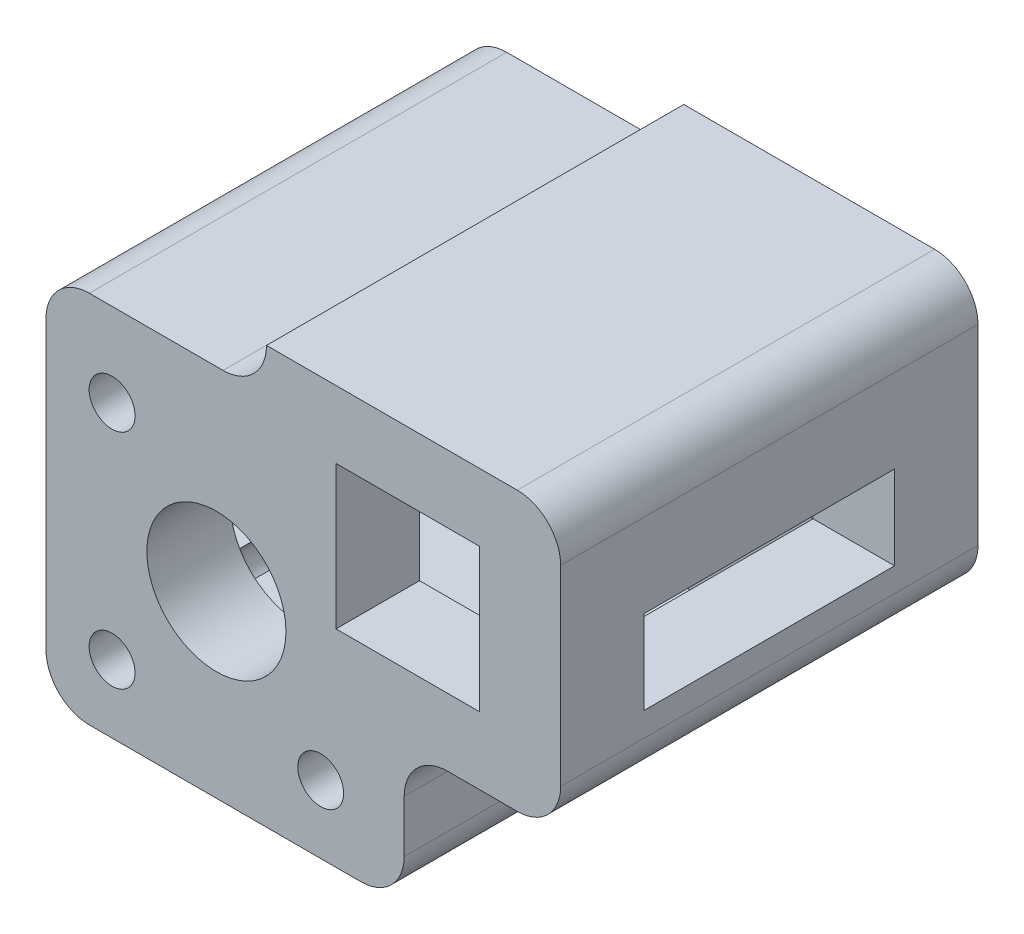
SolidWorks part; units mm, degrees
material "ABS"
ref_plane "前视基准面" through (0, 0, 0) normal (0, 0, 1) x (1, 0, 0)
ref_plane "上视基准面" through (0, 0, 0) normal (0, 1, 0) x (1, 0, 0)
ref_plane "右视基准面" through (0, 0, 0) normal (1, 0, 0) x (0, 0, -1)
sketch "草图1" plane through (0, 0, 0) normal (0, 0, 1) x (1, 0, 0)
  line L1 (-18.5, 15) -> (18.5, 15)
  line L2 (-18.5, 15) -> (-18.5, -15)
  line L3 (-18.5, -15) -> (18.5, -15)
  line L4 (18.5, 15) -> (18.5, -15)
  line L5 (-18.5, 15) -> (18.5, -15) construction
  line L6 (-18.5, -15) -> (18.5, 15) construction
  line L11 (2.5, 10) -> (12.5, 10) construction
  line L12 (2.5, 10) -> (2.5, 0) construction
  line L17 (2.5, 0) -> (12.5, 0) construction
  line L18 (12.5, 10) -> (12.5, 0) construction
  line L23 (2.5, 10) -> (12.5, 0) construction
  line L24 (2.5, 0) -> (12.5, 10) construction
  line L25 (2.35, 10.15) -> (12.65, 10.15)
  line L26 (2.35, 10.15) -> (2.35, -0.15)
  line L27 (2.35, -0.15) -> (12.65, -0.15)
  line L28 (12.65, 10.15) -> (12.65, -0.15)
  line L29 (2.35, 10.15) -> (12.65, -0.15) construction
  line L30 (2.35, -0.15) -> (12.65, 10.15) construction
  point P0 (0, 0)
  point P5 (7.5, 5)
  point P9 (7.5, 5)
  dimension "D1" = 30
  dimension "D2" = 37
  dimension "D3" = 10
  dimension "D4" = 5
  dimension "D5" = 6
  dimension "D6" = 10.3
extrude "凸台-拉伸1" add sketch "草图1" along normal blind 30
sketch "草图2" plane through (0, 0, 30) normal (0, 0, 1) x (1, 0, 0)
  line L1 (-18.5, -15) -> (18.5, -15) construction
  line L2 (-18.5, 15) -> (-18.5, -15) construction
  line L3 (-0.5, 0) -> (17.5, 0) construction
  line L4 (18.5, -15) -> (7.25, -15)
  line L5 (18.5, -15) -> (18.5, -5)
  line L6 (18.5, -5) -> (7.25, -5)
  line L7 (7.25, -15) -> (7.25, -5)
  circle A0 centre (-13.75, 5.8805) radius 1.65
  circle A1 centre (-13.75, -10.1195) radius 1.65
  circle A2 centre (1.25, -10.1195) radius 1.65
  dimension "D1" = 3.3
  dimension "D2" = 3.3
  dimension "D3" = 3.3
  dimension "D4" = 4.8805
  dimension "D5" = 4.75
  dimension "D6" = 4.75
  dimension "D7" = 16
  dimension "D8" = 4.8805
  dimension "D9" = 15
  dimension "D10" = 5
  dimension "D11" = 6
extrude "切除-拉伸1" cut sketch "草图2" against normal through all
sketch "草图3" plane through (0, 0, 30) normal (0, 0, 1) x (1, 0, 0)
  line L8 (2.35, 10.15) -> (2.35, -0.15) construction
  line L9 (-18.5, 15) -> (-2.65, 15)
  line L10 (-18.5, 15) -> (-18.5, 11.8805)
  line L11 (-18.5, 11.8805) -> (-2.65, 11.8805)
  line L12 (-2.65, 15) -> (-2.65, 11.8805)
  line L14 (-13.75, 5.8805) -> (1.25, 5.8805) construction
  line L15 (-13.75, 5.8805) -> (-13.75, -10.1195) construction
  line L16 (-13.75, -10.1195) -> (1.25, -10.1195) construction
  line L17 (1.25, 5.8805) -> (1.25, -10.1195) construction
  circle A2 centre (-13.75, 5.8805) radius 1.65 construction
  circle A3 centre (-6.25, -2.1195) radius 5
  dimension "D3" = 10
  dimension "D1" = 6
  dimension "D2" = 5
extrude "切除-拉伸2" cut sketch "草图3" against normal through all
sketch "草图4" plane through (-18.5, 0, 0) normal (-1, 0, 0) x (0, 0, 1)
  line L0 (30, -15) -> (0, -15) construction
  line L1 (24, 5.8805) -> (6, 5.8805)
  line L2 (24, 5.8805) -> (24, -9)
  line L3 (24, -9) -> (6, -9)
  line L4 (6, 5.8805) -> (6, -9)
  line L5 (24, 5.8805) -> (6, -9) construction
  line L6 (24, -9) -> (6, 5.8805) construction
  line L7 (30, 11.8805) -> (30, -15) construction
  line L8 (0, 11.8805) -> (0, -15) construction
  line L9 (0, 11.8805) -> (30, 11.8805) construction
  point P0 (15, -1.5598)
  dimension "D1" = 6
  dimension "D2" = 6
  dimension "D3" = 6
  dimension "D4" = 6
extrude "切除-拉伸3" cut sketch "草图4" against normal through all
sketch "草图5" plane through (0, 0, 6) normal (0, 0, 1) x (1, 0, 0)
  line L1 (18.5, -5) -> (12.65, -5)
  line L2 (18.5, -5) -> (18.5, -0.15)
  line L3 (18.5, -0.15) -> (12.65, -0.15)
  line L4 (12.65, -5) -> (12.65, -0.15)
  point P4 (13.65, -0.15)
  point P5 (13.3932, 0.1068)
  point P8 (12.65, -0.15)
extrude "凸台-拉伸2" add sketch "草图5" along normal up to surface (18 mm away) up to face at (-0.5, -1.8504, 24)
fillet "圆角2" radius 3.12 8 edges at (-18.5, 11.8805, 15) (18.5, 15, 15) (18.5, -5, 15) (7.25, -5, 3) (7.25, -5, 27) (7.25, -15, 15) (-18.5, -15, 15) (-2.65, 11.8805, 15)
